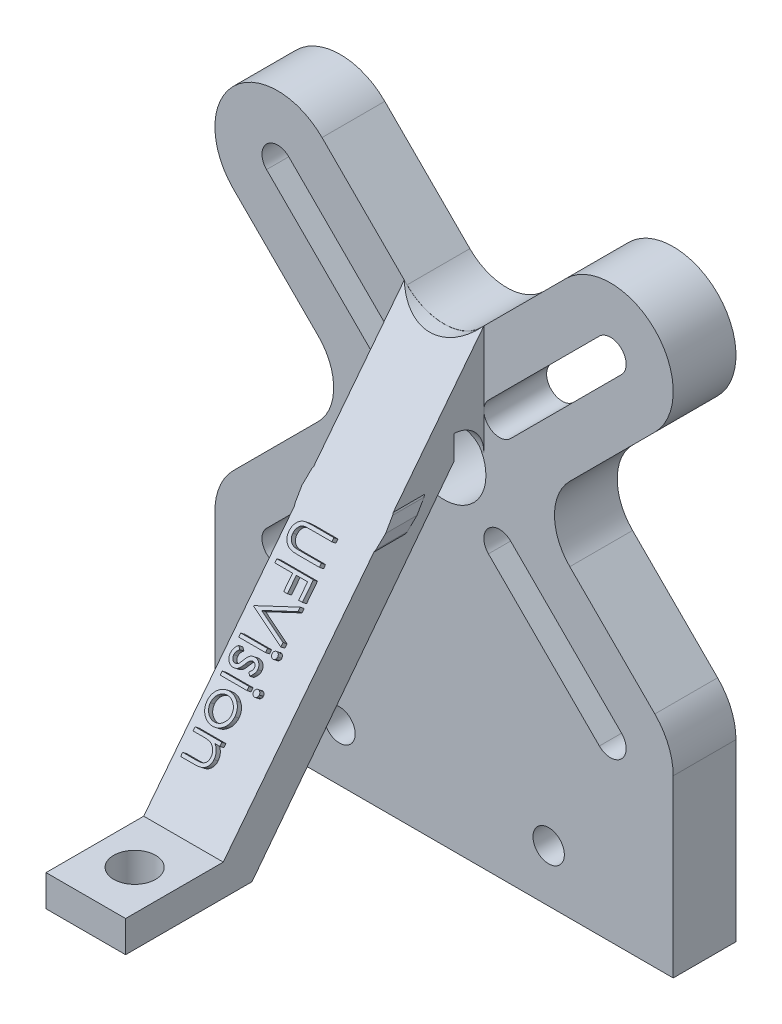
SolidWorks part; units mm, degrees
material "Plástico personalizado"
ref_plane "Plano frontal" through (0, 0, 0) normal (0, 0, 1) x (1, 0, 0)
ref_plane "Plano superior" through (0, 0, 0) normal (0, 1, 0) x (1, 0, 0)
ref_plane "Plano direito" through (0, 0, 0) normal (1, 0, 0) x (0, 0, -1)
sketch "Esboço1" plane through (0, 0, 0) normal (0, 0, 1) x (1, 0, 0)
  line L0 (-15.9099, -15.9099) -> (-5.3033, -5.3033) construction
  line L1 (-16.9706, -14.8492) -> (-6.364, -4.2426)
  line L2 (-14.8492, -16.9706) -> (-4.2426, -6.364)
  line L3 (-15.9099, 15.9099) -> (15.9099, -15.9099) construction
  line L4 (-11.6673, 20.1525) -> (20.1525, -11.6673)
  line L5 (-20.1525, 11.6673) -> (11.6673, -20.1525)
  line L6 (15.9099, 15.9099) -> (-15.9099, -15.9099) construction
  line L7 (20.1525, 11.6673) -> (-11.6673, -20.1525)
  line L8 (11.6673, 20.1525) -> (-20.1525, -11.6673)
  line L9 (5.3033, -5.3033) -> (15.9099, -15.9099) construction
  line L12 (5.3033, 5.3033) -> (15.9099, 15.9099) construction
  line L13 (4.2426, 6.364) -> (14.8492, 16.9706)
  line L14 (6.364, 4.2426) -> (16.9706, 14.8492)
  line L15 (-15.9099, 15.9099) -> (-5.3033, 5.3033) construction
  line L18 (6.364, -4.2426) -> (16.9706, -14.8492)
  line L21 (4.2426, -6.364) -> (14.8492, -16.9706)
  line L22 (-14.8492, 16.9706) -> (-4.2426, 6.364)
  line L23 (-16.9706, 14.8492) -> (-6.364, 4.2426)
  line L24 (-21.9099, -32.6502) -> (21.9099, -32.6502)
  line L25 (21.9099, -32.6502) -> (21.9099, -15.9099)
  line L26 (-21.9099, -32.6502) -> (-21.8861, -15.3755)
  line L27 (-15.9099, -21.9099) -> (-21.8951, -21.9099)
  line L28 (-15.9099, -21.9099) -> (15.9099, -21.9099)
  line L29 (15.9099, -21.9099) -> (21.9099, -21.9099)
  arc A0 (-11.6673, 20.1525) -> (-20.1525, 11.6673) centre (-15.9099, 15.9099) ccw
  arc A1 (11.6673, -20.1525) -> (20.1525, -11.6673) centre (15.9099, -15.9099) ccw
  arc A2 (20.1525, 11.6673) -> (11.6673, 20.1525) centre (15.9099, 15.9099) ccw
  arc A3 (-20.1525, -11.6673) -> (-11.6673, -20.1525) centre (-15.9099, -15.9099) ccw
  arc A6 (4.2426, 6.364) -> (6.364, 4.2426) centre (5.3033, 5.3033) ccw
  arc A7 (16.9706, 14.8492) -> (14.8492, 16.9706) centre (15.9099, 15.9099) ccw
  arc A12 (-16.9706, -14.8492) -> (-14.8492, -16.9706) centre (-15.9099, -15.9099) ccw
  arc A13 (-4.2426, -6.364) -> (-6.364, -4.2426) centre (-5.3033, -5.3033) ccw
  arc A14 (6.364, -4.2426) -> (4.2426, -6.364) centre (5.3033, -5.3033) ccw
  arc A15 (14.8492, -16.9706) -> (16.9706, -14.8492) centre (15.9099, -15.9099) ccw
  arc A16 (-14.8492, 16.9706) -> (-16.9706, 14.8492) centre (-15.9099, 15.9099) ccw
  arc A17 (-6.364, 4.2426) -> (-4.2426, 6.364) centre (-5.3033, 5.3033) ccw
  circle A18 centre (0, 0) radius 4
  point P4 (-10.6066, -10.6066)
  point P8 (0, 0)
  point P14 (0, 0)
  point P25 (10.6066, -10.6066)
  point P28 (10.6066, 10.6066)
  point P35 (-10.6066, 10.6066)
  dimension "D12" = 0
  dimension "D17" = 8
  dimension "D2" = 3
  dimension "D3" = 15
  dimension "D4" = 15
  dimension "D5" = 15
  dimension "D6" = 0
  dimension "D7" = 15
  dimension "D8" = 45
  dimension "D9" = 45
  dimension "D10" = 0
  dimension "D11" = 3
  dimension "D13" = 3
  dimension "D14" = 12
  dimension "D15" = 12
  dimension "D16" = 3
  dimension "D18" = 43.8198
  dimension "D19" = 17.2746
extrude "Ressalto-extrusão1" add sketch "Esboço1" along normal blind 6 contours L29 L28 L27 L26 L24 L25 | A3 L26 L27 | A1 L29 L25 | A3 L28 A1 L5 L7 | A13 L5 L8 A3 L26 L7 L2 A12 L1 | A15 L21 A14 L7 L5 A1 L4 L18 | L4 L8 L5 L7 A18 | A17 L23 A16 L22 L8 L4 A0 L5 | A7 L14 A6 L4 L7 A2 L8 L13 region at (-2.3403, -6.5829, 0) region at (-6.1943, -1.9516, 0) region at (-14.0998, 6.0527, 0) region at (2.3404, -6.5831, 0) region at (0, -17.4701, 0) region at (6.0527, 14.0998, 0) region at (0.0037, -27.2803, 0) region at (20.5697, -20.5697, 0) region at (-20.5512, -20.5931, 0)
sketch "Esboço2" plane through (0, 0, 6) normal (0, 0, 1) x (1, 0, 0)
  line L0 (0, -32.6502) -> (0, 14.3657) construction
  line L1 (-21.9099, -32.6502) -> (21.9099, -32.6502) construction
  line L2 (-21.9099, -32.6502) -> (-21.903, -27.6502)
  line L3 (-21.9099, -32.6502) -> (-21.8861, -15.3755) construction
  line L4 (-21.903, -27.6502) -> (21.9099, -27.6502) construction
  line L5 (21.9099, -32.6502) -> (21.9099, -15.9099) construction
  circle A0 centre (-10, -27.6502) radius 1.5
  circle A1 centre (10, -27.6502) radius 1.5
  dimension "D1" = 20
  dimension "D2" = 10
extrude "Corte-extrusão1" cut sketch "Esboço2" against normal blind 6 contours A0 | A1 region at (-10, -27.6502, 6) region at (10, -27.6502, 6)
fillet "Filete1" radius 5 3 edges at (0, 8.4853, 3) (8.4853, 0, 3) (-8.4853, 0, 3)
sketch "Esboço3" plane through (0, 0, 6) normal (0, 0, 1) x (1, 0, 0)
  line L0 (-3.8033, 12.2886) -> (-3.8033, 1.1847)
  line L1 (-11.6673, 20.1525) -> (-3.5355, 12.0208) construction
  line L2 (-21.9099, -32.6502) -> (21.9099, -32.6502) construction
  line L3 (3.8033, 12.2886) -> (3.8033, 1.1847)
  line L4 (11.6673, 20.1525) -> (3.5355, 12.0208) construction
  line L5 (-4, 0) -> (-3.8649, 1.0307)
  line L6 (-3.8649, 1.0307) -> (-3.8033, 1.1847)
  line L7 (-4, 0) -> (-3.8649, -1.0307)
  line L8 (-3.8649, -1.0307) -> (-3.8033, -1.1847)
  line L9 (-3.8033, -1.1847) -> (-3.8033, -32.6502)
  line L10 (4, 0) -> (3.8649, 1.0307)
  line L11 (3.8649, 1.0307) -> (3.8033, 1.1847)
  line L12 (4, 0) -> (3.8649, -1.0307)
  line L13 (3.8649, -1.0307) -> (3.8033, -1.1847)
  line L14 (3.8033, -1.1847) -> (3.8033, -32.6502)
  line L15 (-3.8033, -32.6502) -> (3.8033, -32.6502)
  arc A1 (-3.8033, 12.2886) -> (3.8033, 12.2886) centre (0, 15.5563) ccw
  circle A2 centre (0, 0) radius 4 construction
  dimension "D2" = 5.0143
  dimension "D1" = 31.4655
  dimension "D3" = 1.0307
  dimension "D4" = 1.0395
  dimension "D5" = 0.1658
  dimension "D6" = 0.1658
extrude "Ressalto-extrusão5" add sketch "Esboço3" along normal blind 50 separate body
sketch "Esboço4" plane through (-3.8033, 0, 0) normal (-1, 0, 0) x (0, 0, 1)
  line L0 (6, 12.2886) -> (41.0551, -32.6502) construction
  line L1 (56, -32.6502) -> (6, -32.6502) construction
  line L2 (6, 12.2886) -> (41.0551, -32.6502)
  line L3 (41.0551, -32.6502) -> (56, -32.6502)
  line L4 (56, -32.6502) -> (56, 12.2886)
  line L5 (56, 12.2886) -> (6, 12.2886)
extrude "Corte-extrusão2" cut sketch "Esboço4" against normal through all both and the other way through all
sketch "Esboço6" plane through (3.8033, 0, 0) normal (1, 0, 0) x (0, 0, -1)
  line L0 (-41.0551, -32.6502) -> (-38.0551, -32.6502) construction
  line L1 (-41.0551, -32.6502) -> (-6, -32.6502) construction
  line L2 (-38.0551, -32.6502) -> (-6, 8.4427)
  line L3 (-6, 1.1847) -> (-6, 12.2886) construction
  line L4 (-6, 8.4427) -> (-6, -32.6502)
  line L5 (-6, -32.6502) -> (-38.0551, -32.6502)
  dimension "D1" = 3
extrude "Corte-extrusão5" cut sketch "Esboço6" against normal through all both and the other way through all
sketch "Esboço7" plane through (0, -32.6502, 0) normal (0, -1, 0) x (-1, 0, 0)
  line L0 (3.8033, -41.0551) -> (3.8033, -46.9814)
  line L1 (-3.8033, -41.0551) -> (-3.8033, -46.9814)
  line L2 (-3.8033, -46.9814) -> (3.8033, -46.9814)
  line L7 (3.8033, -41.0551) -> (3.8033, -38.0551)
  line L8 (3.8033, -38.0551) -> (-3.8033, -38.0551)
  line L9 (-3.8033, -38.0551) -> (-3.8033, -41.0551)
  line L10 (-3.8033, -41.0551) -> (3.8033, -41.0551)
  line L11 (3.8033, -41.0551) -> (3.8033, -38.0551)
  line L12 (3.8033, -38.0551) -> (-3.8033, -38.0551)
  line L13 (-3.8033, -38.0551) -> (-3.8033, -41.0551)
  dimension "D1" = 0
extrude "Ressalto-extrusão6" add sketch "Esboço7" against normal blind 3
sketch "Esboço8" plane through (0, -29.6502, 0) normal (0, 1, 0) x (1, 0, 0)
  circle A0 centre (0, -42.8481) radius 2
extrude "Corte-extrusão6" cut sketch "Esboço8" along normal blind 3 and the other way through all
sketch "Esboço9" plane through (0, 0, 6) normal (0, 0, 1) x (1, 0, 0)
  line L0 (-10, -26.1502) -> (-10, -22.6502) construction
  line L1 (-10, -22.6502) -> (9.8776, -22.6502) construction
  line L2 (-10, -26.1502) -> (-10, -22.6502)
  line L3 (-10, -22.6502) -> (9.8776, -22.6502)
  line L4 (9.8776, -22.6502) -> (10, -26.1502)
  line L5 (10, -26.1502) -> (-10, -26.1502)
  circle A0 centre (-10, -27.6502) radius 1.5 construction
  circle A1 centre (10, -27.6502) radius 1.5 construction
  dimension "D1" = 3.5
extrude "Corte-extrusão7" cut sketch "Esboço9" along normal blind 30
sketch "Esboço10" plane through (0, -22.6502, 0) normal (0, -1, 0) x (-1, 0, 0)
  line L0 (3.8033, -33.2544) -> (3.8033, -40.2544)
  line L1 (-3.8033, -33.2544) -> (-3.8033, -40.2544)
  line L2 (-3.8033, -40.2544) -> (3.8033, -40.2544)
  line L3 (3.8033, -33.2544) -> (-3.8033, -33.2544)
  dimension "D1" = 7
extrude "Ressalto-extrusão7" add sketch "Esboço10" against normal blind 3 separate body
sketch "Esboço11" plane through (0, -19.6502, 0) normal (0, 1, 0) x (1, 0, 0)
  line L0 (-3.8033, -33.2544) -> (-3.8033, -30.3145)
  line L1 (-3.8033, -33.2544) -> (-3.8033, -16.51) construction
  line L2 (-3.8033, -30.3145) -> (3.8033, -30.2544)
  line L3 (3.8033, -30.2544) -> (3.8033, -33.2544)
  line L4 (3.8033, -33.2544) -> (-3.8033, -33.2544)
extrude "Ressalto-extrusão8" add sketch "Esboço11" against normal blind 3
sketch "Esboço12" plane through (0, -19.6502, 0) normal (0, 1, 0) x (1, 0, 0)
  circle A0 centre (0, -35.5843) radius 2
  dimension "D1" = 4
extrude "Corte-extrusão8" cut sketch "Esboço12" against normal blind 3
sketch "Esboço13" plane through (-3.8033, 0, 0) normal (-1, 0, 0) x (0, 0, 1)
  line L0 (8.8309, 4.8137) -> (6, 4.8137)
  line L1 (6, 8.4427) -> (11.6618, 1.1847) construction
  line L2 (6, 11.6673) -> (6, 3.5355) construction
  line L3 (6, 4.8137) -> (6, 8.4427)
  line L4 (6, 8.4427) -> (8.8309, 4.8137)
extrude "Ressalto-extrusão9" add sketch "Esboço13" against normal up to surface (7.6066 mm away) up to face at (3.8033, 5.7752, 9.5809)
sketch "Esboço14" plane through (-3.8033, 0, 0) normal (-1, 0, 0) x (0, 0, 1)
  line L0 (8.8309, 4.8137) -> (8.8309, 2.5396)
  line L1 (8.8309, 2.5396) -> (28.1663, -22.6502)
  line L2 (28.1663, -22.6502) -> (30.2544, -22.6502)
  line L3 (30.2544, -22.6502) -> (8.8309, 4.8137)
extrude "Ressalto-extrusão10" add sketch "Esboço14" against normal up to surface (7.6066 mm away) up to face at (3.8033, -14.495, 28.6162)
fillet "Filete3" radius 3 1 edges at (0, 4.8137, 6)
sketch "Esboço15" plane through (0, 7.5586, 9.6897) normal (0, 0.6151, 0.7885) x (1, 0, 0)
  line L0 (-2.8546, -11.0888) -> (-2.8546, -34.5079) construction
  line L1 (3.8033, -34.5079) -> (-3.8033, -34.5079) construction
  text T0 "UFVision"
extrude "Ressalto-extrusão11" add sketch "Esboço15" along normal blind 0.5
